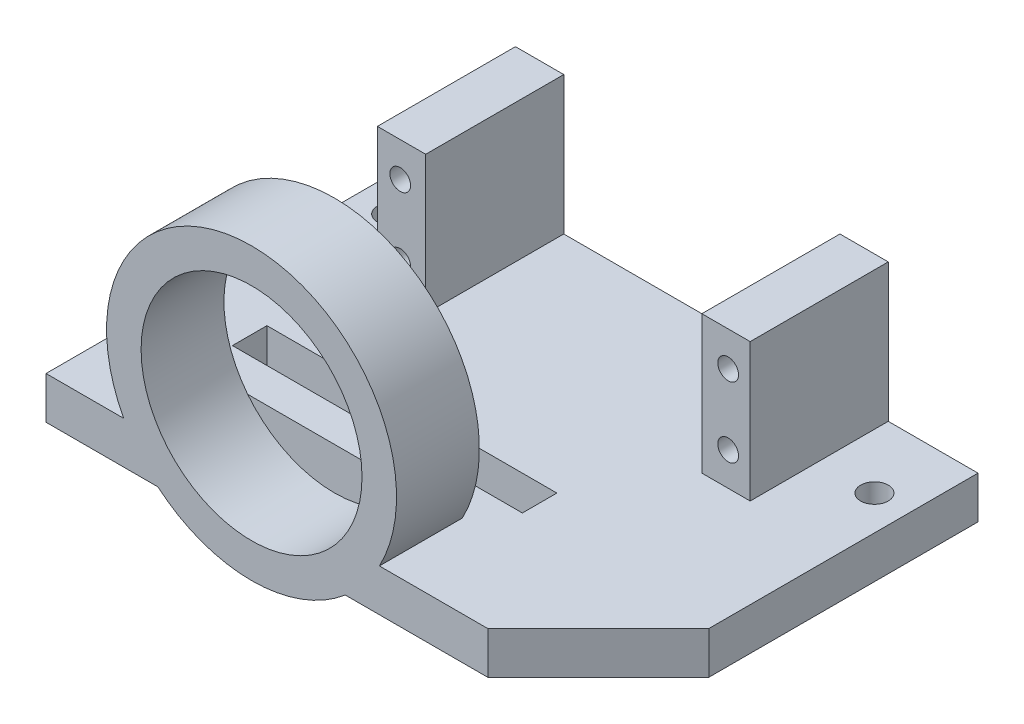
SolidWorks part; units mm, degrees
ref_plane "Front Plane" through (0, 0, 0) normal (0, 0, 1) x (1, 0, 0)
ref_plane "Top Plane" through (0, 0, 0) normal (0, 1, 0) x (1, 0, 0)
ref_plane "Right Plane" through (0, 0, 0) normal (1, 0, 0) x (0, 0, -1)
sketch "Sketch1" plane through (0, 0, 0) normal (0, 1, 0) x (1, 0, 0)
  line L1 (0, 0) -> (80, 0)
  line L2 (0, 0) -> (0, 20)
  line L3 (0, 20) -> (80, 20)
  line L4 (80, 0) -> (80, 20)
  dimension "D1" = 80
  dimension "D2" = 20
extrude "Boss-Extrude1" add sketch "Sketch1" along normal blind 6.12
sketch "Sketch14" plane through (0, 6.12, 0) normal (0, 1, 0) x (1, 0, 0)
  line L0 (80, 0) -> (80, 20) construction
  line L1 (0, 20) -> (0, 0) construction
  line L2 (0, 0) -> (80, 0) construction
  circle A0 centre (75, 10) radius 2
  circle A1 centre (5, 10) radius 2
  dimension "D1" = 4
  dimension "D2" = 5
  dimension "D3" = 5
  dimension "D4" = 10
  dimension "D5" = 10
extrude "Cut-Extrude7" cut sketch "Sketch14" against normal blind 22.92
sketch "Sketch2" plane through (0, 6.12, 0) normal (0, 1, 0) x (1, 0, 0)
  line L0 (0, 0) -> (80, 0) construction
  line L1 (13, 0) -> (20, 0)
  line L2 (13, 0) -> (13, 20)
  line L3 (13, 20) -> (20, 20)
  line L4 (20, 0) -> (20, 20)
  line L5 (80, 20) -> (0, 20) construction
  line L7 (60, 0) -> (67, 0)
  line L8 (60, 0) -> (60, 20)
  line L9 (60, 20) -> (67, 20)
  line L10 (67, 0) -> (67, 20)
  dimension "D1" = 7
  dimension "D2" = 7
  dimension "D3" = 40
  dimension "D4" = 20
extrude "Boss-Extrude2" add sketch "Sketch2" along normal blind 20
sketch "Sketch3" plane through (0, 0, 0) normal (0, 0, 1) x (1, 0, 0)
  line L1 (0, 6.12) -> (80, 6.12)
  line L2 (0, 6.12) -> (0, 0)
  line L3 (0, 0) -> (80, 0)
  line L4 (80, 6.12) -> (80, 0)
extrude "Boss-Extrude3" add sketch "Sketch3" along normal blind 35
sketch "Sketch4" plane through (0, 0, 35) normal (0, 0, 1) x (1, 0, 0)
  circle A0 centre (29.774, 16.026) radius 16
  arc A1 (44.9389, 10.9244) -> (14.6091, 21.1276) centre (29.774, 16.026) ccw construction
sketch "Sketch5" plane through (0, 0, 35) normal (0, 0, 1) x (1, 0, 0)
  circle A1 centre (29.774, 16.026) radius 21
  dimension "D1" = 42
extrude "Boss-Extrude4" add sketch "Sketch5" against normal blind 12
extrude "Cut-Extrude1" cut sketch "Sketch4" against normal blind 12
sketch "Sketch6" plane through (0, 0, 23) normal (0, 0, -1) x (-1, 0, 0)
  line L0 (-48.0686, 26.3365) -> (-11.4794, 26.3365)
  arc A0 (-48.0686, 26.3365) -> (-11.4794, 26.3365) centre (-29.774, 16.026) cw
  arc A1 (-11.2572, 6.12) -> (-48.2908, 6.12) centre (-29.774, 16.026) ccw construction
  dimension "D1" = 10.3105
sketch "Sketch7" plane through (0, 0, 0) normal (0, 0, 1) x (1, 0, 0)
  circle A0 centre (16.312, 21.106) radius 1.5
  circle A1 centre (16.312, 10.946) radius 1.5
  circle A2 centre (63.81, 10.946) radius 1.5
  circle A3 centre (63.81, 21.106) radius 1.5
  dimension "D1" = 3
extrude "Cut-Extrude2" cut sketch "Sketch7" against normal blind 12
sketch "Sketch8" plane through (0, 6.12, 0) normal (0, 1, 0) x (1, 0, 0)
  line L0 (0, 20) -> (0, -35) construction
  line L1 (10, -18) -> (52, -18)
  line L2 (10, -18) -> (10, -13)
  line L3 (10, -13) -> (52, -13)
  line L4 (52, -18) -> (52, -13)
  line L6 (13, 20) -> (0, 20) construction
  dimension "D1" = 5
  dimension "D2" = 10
  dimension "D3" = 42
  dimension "D4" = 33
extrude "Cut-Extrude3" cut sketch "Sketch8" against normal blind 12 contours L4 L3 L2 L1
sketch "Sketch9" plane through (0, 6.12, 0) normal (0, 1, 0) x (1, 0, 0)
  line L0 (80, -19) -> (64, -35)
  line L1 (80, -35) -> (80, 20) construction
  line L2 (80, -35) -> (48.2908, -35) construction
  line L3 (64, -35) -> (80, -35)
  line L4 (80, -35) -> (80, -19)
  dimension "D1" = 16
  dimension "D2" = 16
extrude "Cut-Extrude4" cut sketch "Sketch9" against normal blind 10
mirror "Mirror2" [suppressed] of bodies 109
sketch "Sketch10" [suppressed] plane through (0, 6.12, 0) normal (0, 1, 0) x (1, 0, 0)
  line L0 (80, -19) -> (80, 59) construction
  line L1 (0, -35) -> (80, -35)
  line L2 (0, -35) -> (0, 20)
  line L3 (0, 20) -> (80, 20)
  line L4 (80, -35) -> (80, 20)
extrude "Cut-Extrude6" [suppressed] cut sketch "Sketch10" against normal blind 20 and the other way blind 40
sketch "Sketch11" [suppressed] plane through (0, 0, 0) normal (0, -1, 0) x (1, 0, 0)
  line L0 (80, -20) -> (80, -59)
  line L1 (80, -59) -> (64, -75)
  line L2 (64, -75) -> (0, -75)
  line L3 (0, -75) -> (0, -20)
  line L4 (0, -20) -> (80, -20)
  line L6 (52, -58) -> (10, -58)
  line L7 (52, -58) -> (52, -53)
  line L8 (52, -53) -> (10, -53)
  line L9 (10, -58) -> (10, -53)
  circle A0 centre (75, -30) radius 2
  circle A1 centre (5, -30) radius 2
extrude "Boss-Extrude5" [suppressed] add sketch "Sketch11" along normal blind 2.92
